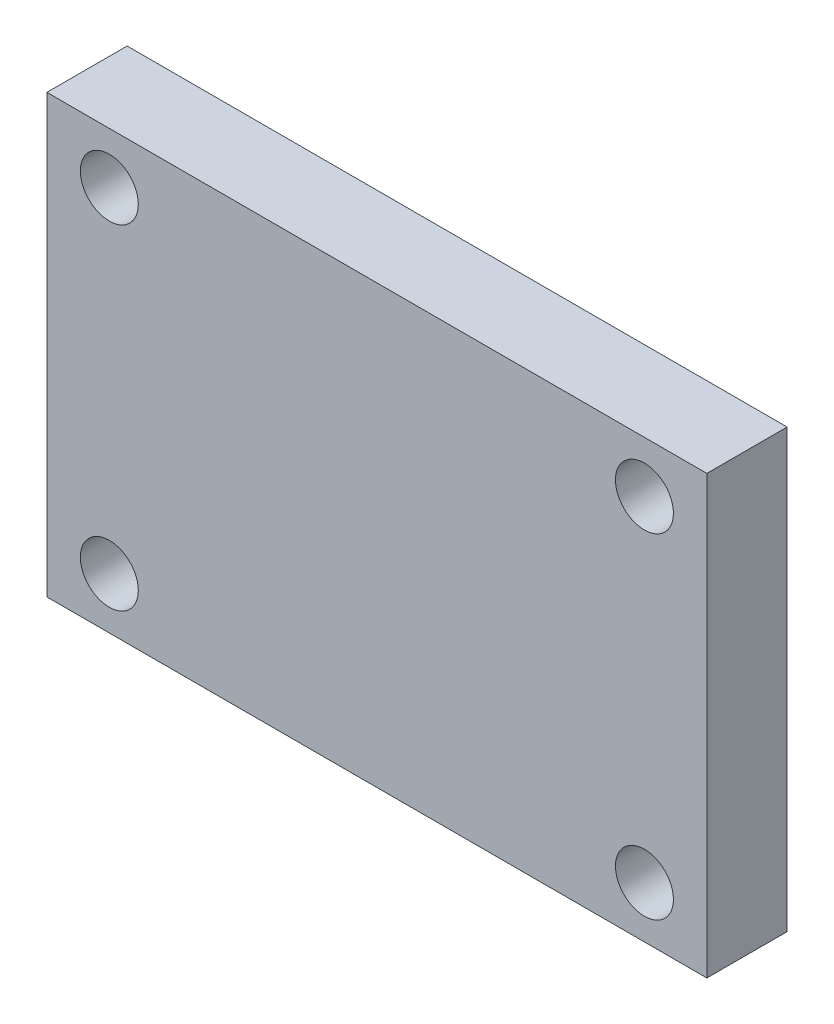
SolidWorks part; units mm, degrees
ref_plane "Front Plane" through (0, 0, 0) normal (0, 0, 1) x (1, 0, 0)
ref_plane "Top Plane" through (0, 0, 0) normal (0, 1, 0) x (1, 0, 0)
ref_plane "Right Plane" through (0, 0, 0) normal (1, 0, 0) x (0, 0, -1)
sketch "Sketch1" plane through (0, 0, 0) normal (0, 0, 1) x (1, 0, 0)
  line L0 (148, 98) -> (-148, 98) construction
  line L1 (148, -98) -> (-148, -98)
  line L2 (148, -98) -> (148, 98)
  line L3 (148, 98) -> (-148, 98)
  line L4 (-148, -98) -> (-148, 98)
  line L5 (148, -98) -> (-148, 98) construction
  line L6 (148, 98) -> (-148, -98) construction
  line L7 (-148, 98) -> (-148, -98) construction
  circle A0 centre (-120, 75) radius 13 construction
  circle A1 centre (-120, -75) radius 13 construction
  circle A2 centre (120, 75) radius 13 construction
  circle A3 centre (120, -75) radius 13 construction
  circle A4 centre (-120, 75) radius 13
  circle A5 centre (-120, -75) radius 13
  circle A6 centre (120, 75) radius 13
  circle A7 centre (120, -75) radius 13
  point P0 (0, 0)
extrude "Extrude1" add sketch "Sketch1" against normal blind 36
